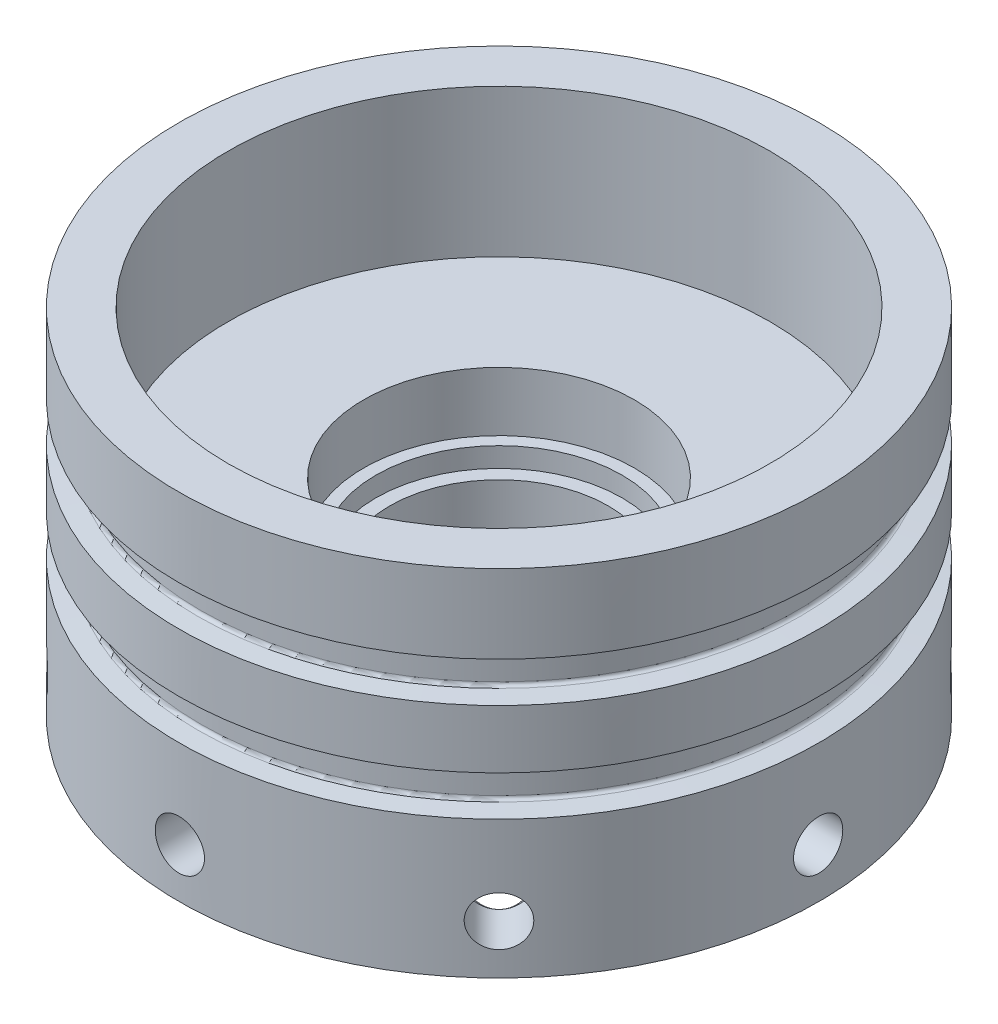
SolidWorks part; units mm, degrees
note: '?' marks a value the reader was unsure of.
material "1060 Alloy"
ref_plane "Front Plane" through (0, 0, 0) normal (0, 0, 1) x (1, 0, 0)
ref_plane "Top Plane" through (0, 0, 0) normal (0, 1, 0) x (1, 0, 0)
ref_plane "Right Plane" through (0, 0, 0) normal (1, 0, 0) x (0, 0, -1)
sketch "Sketch1" plane through (0, 0, 0) normal (0, 0, 1) x (1, 0, 0)
  line L0 (0, 0) -> (0, 25.4) construction
  line L1 (-41.275, 13.97) -> (-41.275, 45.72)
  line L2 (-34.925, 13.97) -> (-18.5341, 13.97)
  line L3 (-14.0891, 0) -> (-14.0891, 16.51)
  line L4 (-17.4625, 26.67) -> (-34.925, 26.67)
  line L5 (-34.925, 26.67) -> (-34.925, 45.72)
  line L6 (-34.925, 45.72) -> (-41.275, 45.72)
  line L7 (-41.275, 13.97) -> (-41.275, 0)
  line L8 (-14.0891, 0) -> (-18.5341, 0)
  line L9 (-15.875, 19.05) -> (-17.4625, 19.05)
  line L10 (-41.275, 0) -> (-34.925, 0)
  line L11 (55, 0) -> (-55, 0) construction
  line L12 (-34.925, 0) -> (-34.925, 13.97)
  line L13 (-17.4625, 19.05) -> (-17.4625, 26.67)
  line L14 (-14.0891, 16.51) -> (-15.875, 16.51)
  line L15 (-15.875, 16.51) -> (-15.875, 19.05)
  line L16 (-18.5341, 0) -> (-18.5341, 13.97)
  dimension "D1" = 14.0891
  dimension "D2" = 34.925
  dimension "D3" = 31.75
  dimension "D4" = 6.35
  dimension "D5" = 12.7
  dimension "D7" = 4.445
  dimension "D8" = 13.97
  dimension "D9" = 13.97
  dimension "D10" = 17.4625
  dimension "D11" = 7.62
  dimension "D12" = 15.875
  dimension "D13" = 2.54
revolve "Revolve1" add sketch "Sketch1" angle 360 about L0
ref_plane "Plane1" through (0, 0, 0) normal (-1, 0, 0) x (0, 0, -1)
ref_plane "Plane2" through (0, 0, 0) normal (-1, 0, 0) x (0, 0, -1)
ref_plane "Plane3" through (0, 0, 0) normal (-1, 0, 0) x (0, 0, -1)
ref_plane "Plane4" through (0, 0, 0) normal (-1, 0, 0) x (0, 0, -1)
ref_plane "Plane5" through (0, 0, 0) normal (-1, 0, 0) x (0, 0, -1)
ref_plane "Plane6" through (0, 0, 0) normal (-1, 0, 0) x (0, 0, -1)
ref_plane "Plane7" through (0, 0, 0) normal (-1, 0, 0) x (0, 0, -1)
ref_plane "Plane8" through (0, 0, 0) normal (-1, 0, 0) x (0, 0, -1)
ref_plane "Plane9" through (0, 0, 0) normal (-1, 0, 0) x (0, 0, -1)
ref_plane "Plane10" through (0, 0, 0) normal (-1, 0, 0) x (0, 0, -1)
ref_plane "Plane11" through (0, 0, 0) normal (-1, 0, 0) x (0, 0, -1)
sketch "Sketch3" plane through (0, 0, 0) normal (-1, 0, 0) x (0, 0, -1)
  line L0 (38.8614, -30.6451) -> (41.3639, -30.4262)
  line L1 (41.3639, -30.4262) -> (41.3639, -35.6138)
  line L2 (41.3639, -35.6138) -> (38.8614, -35.3949)
  line L3 (38.4556, -34.9521) -> (38.4556, -31.0879)
  line L4 (0, 50) -> (0, -50) construction
  arc A0 (38.8614, -35.3949) -> (38.4556, -34.9521) centre (38.9001, -34.9521) cw
  arc A1 (38.4556, -31.0879) -> (38.8614, -30.6451) centre (38.9001, -31.0879) cw
  dimension "D4" = 0.4445
  dimension "D5" = 0.4445
  dimension "D1" = 5.1877
  dimension "D2" = 2.5025
  dimension "D3" = 3.8642
  dimension "D6" = 2.5025
  dimension "D7" = 85
  dimension "D8" = 85
  dimension "D9" = 95
revolve "Groove for AS 568-234, O-Ring1" cut sketch "Sketch3"
pattern_linear "LPattern1" count 2 spacing 12.7 along (0, -1, 0) of "Groove for AS 568-234, O-Ring1"
ref_plane "Plane12" through (0, 6.35, 0) normal (0, -1, 0) x (-1, 0, 0)
ref_axis "Axis1" through (-88.99, 6.35, 0) along (1, 0, 0)?
hole_wizard "1/4 (0.25) Diameter Hole1" positions "3DSketch2" profile "Sketch5" hole size "1/4" standard "ANSI Inch"
sketch3d "3DSketch2"
  line L1 (-88.99, 6.35, 0) -> (88.99, 6.35, 0) construction
  point P4 (41.275, 6.35, 0)
sketch "Sketch5" plane through (41.275, 6.35, 0) normal (0, 1, 0) x (0, 0, -1)
  line L0 (0, 0) -> (0, 8.2577)
  line L1 (0, 8.2577) -> (3.175, 6.35)
  line L2 (3.175, 6.35) -> (3.175, 0)
  line L5 (3.175, 0) -> (0, 0)
  line L10 (0, 8.2577) -> (-3.175, 6.35) construction
  line L11 (0, -6.35) -> (0, 107.95) construction
  dimension "Hole Dia." = 6.35
  dimension "Hole Depth" = 6.35
  dimension "Drill Angle" = 118
ref_axis "Axis2" through (0, -2.286, 0) along (0, 1, 0)?
pattern_circular "CirPattern1" count 8 over 360 about axis through (0, -2.286, 0) along (0, 1, 0) of "1/4 (0.25) Diameter Hole1"
sketch "Sketch6" plane through (0, 0, 0) normal (0, 0, 1) x (1, 0, 0)
  line L0 (0, -2.286) -> (0, 48.006) construction
  line L1 (0, -1.5396) -> (76.7104, -1.5396)
  line L2 (0, -1.5396) -> (0, 72.1727)
  line L3 (0, 72.1727) -> (76.7104, 72.1727)
  line L4 (76.7104, -1.5396) -> (76.7104, 72.1727)
revolve "Cut-Revolve1" [suppressed] cut sketch "Sketch6" angle 315 mid plane about axis through (0, -2.286, 0) along (0, 1, 0)
thread "Thread1" [suppressed] pitch 3.6286 start angle 0, offset 0, length 0, pitch 3.6286, diameter 28.1781
ref_plane "Plane13" through (14.0891, 0, 0) normal (0, 0, 1) x (1, 0, 0)
sketch "Thread Profile1" plane through (14.0891, 0, 0) normal (0, 0, 1) x (1, 0, 0)
  line L0 (0, 0) -> (0, 3.6286) construction
  line L1 (0, 0) -> (1.964, 1.1339)
  line L2 (1.964, 1.1339) -> (1.964, 1.5875)
  line L3 (1.964, 1.5875) -> (0, 2.7214)
  line L4 (1.964, 1.3607) -> (0, 1.3607) construction
  line L11 (0, 0) -> (0, 2.7214)
  point P2 (0, 0)
  dimension "Pitch" = 3.6286
  dimension "Profile_Angle" = 60
  dimension "Profile_Land" = 0.4536
  dimension "Profile_Height" = 1.964
